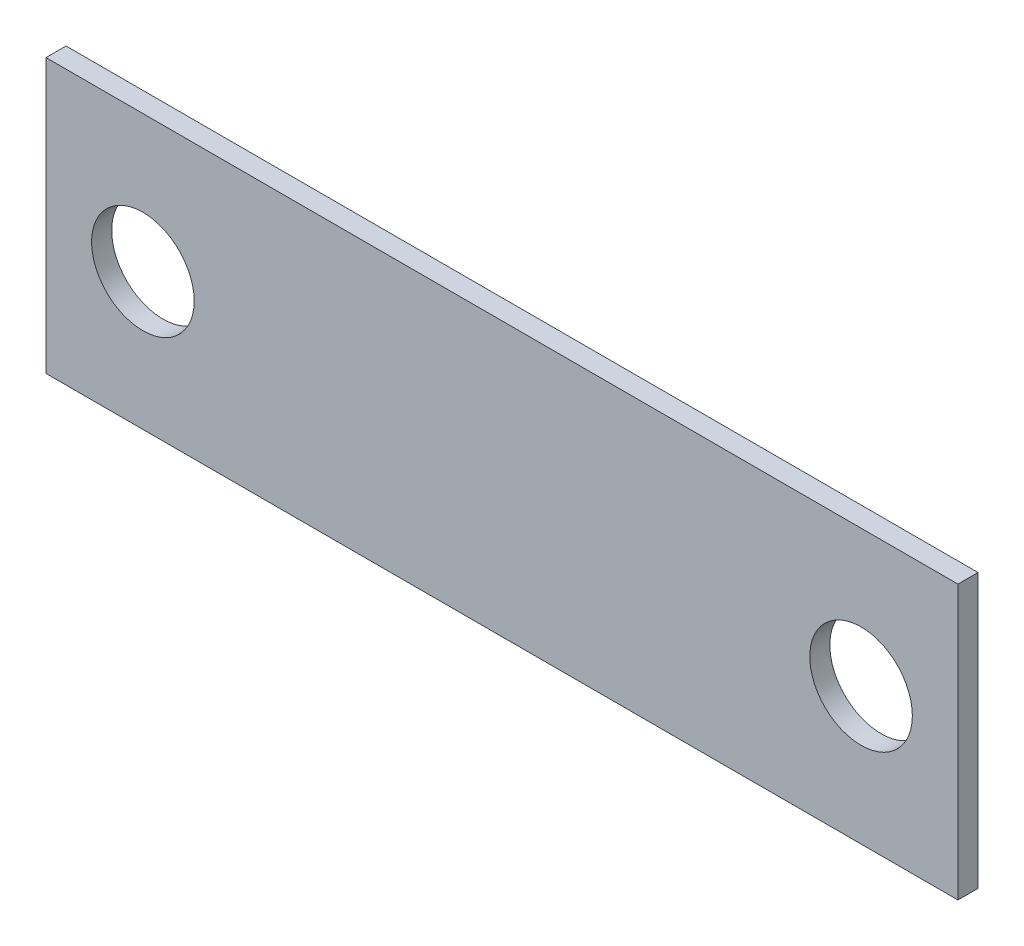
SolidWorks part; units mm, degrees
ref_plane "Front Plane" through (0, 0, 0) normal (0, 0, 1) x (1, 0, 0)
ref_plane "Top Plane" through (0, 0, 0) normal (0, 1, 0) x (1, 0, 0)
ref_plane "Right Plane" through (0, 0, 0) normal (1, 0, 0) x (0, 0, -1)
sketch "Sketch1" plane through (0, 0, 0) normal (0, 0, 1) x (1, 0, 0)
  line L1 (-127, -38.1) -> (127, -38.1)
  line L2 (-127, -38.1) -> (-127, 38.1)
  line L3 (-127, 38.1) -> (127, 38.1)
  line L4 (127, -38.1) -> (127, 38.1)
  line L5 (-127, -38.1) -> (127, 38.1) construction
  line L6 (-127, 38.1) -> (127, -38.1) construction
  point P0 (0, 0)
  dimension "D1" = 254
  dimension "D2" = 76.2
extrude "Boss-Extrude1" add sketch "Sketch1" along normal blind 5.588
sketch "Sketch2" plane through (0, 0, 5.588) normal (0, 0, 1) x (1, 0, 0)
  line L0 (-100.0125, 0) -> (100.0125, 0) construction
  line L2 (-114.3, 38.1) -> (-114.3, -38.1) construction
  line L3 (127, 38.1) -> (-127, 38.1) construction
  line L4 (-127, -38.1) -> (127, -38.1) construction
  line L5 (-127, 38.1) -> (-127, -38.1) construction
  circle A0 centre (-100.0125, 0) radius 14.2875
  circle A1 centre (100.0125, 0) radius 14.2875
  point P4 (0, 0)
  dimension "D1" = 28.575
  dimension "D2" = 12.7
extrude "Cut-Extrude1" cut sketch "Sketch2" against normal through all
